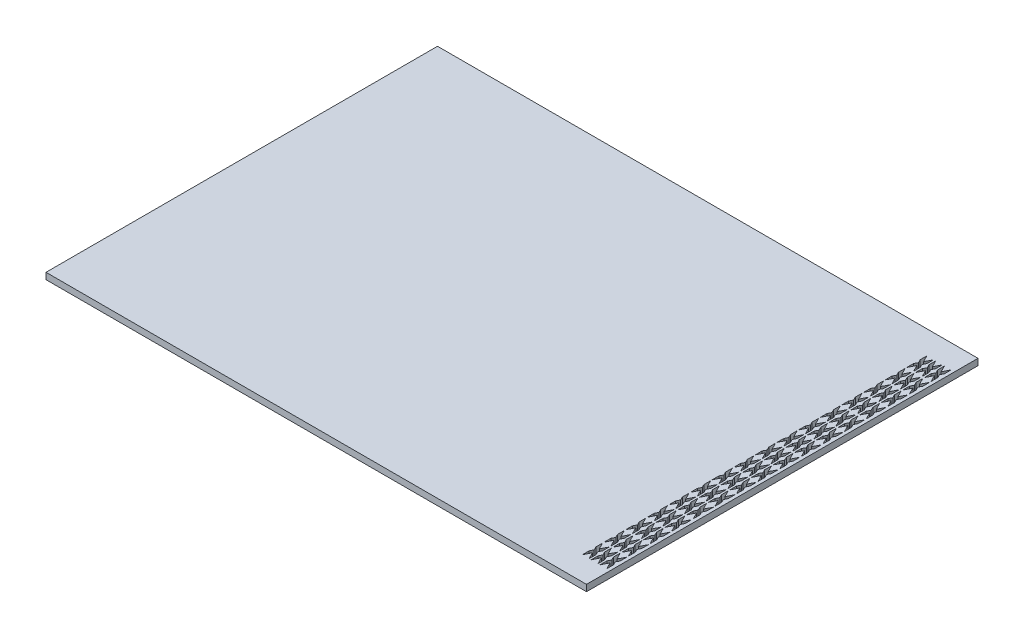
SolidWorks part; units mm, degrees
ref_plane "Front Plane" through (0, 0, 0) normal (0, 0, 1) x (1, 0, 0)
ref_plane "Top Plane" through (0, 0, 0) normal (0, 1, 0) x (1, 0, 0)
ref_plane "Right Plane" through (0, 0, 0) normal (1, 0, 0) x (0, 0, -1)
sketch "Sketch1" plane through (0, 0, 0) normal (0, 1, 0) x (1, 0, 0)
  line L1 (-66.3921, 26.7316) -> (136.8079, 26.7316)
  line L2 (-66.3921, 26.7316) -> (-66.3921, -120.4614)
  line L3 (-66.3921, -120.4614) -> (136.8079, -120.4614)
  line L4 (136.8079, 26.7316) -> (136.8079, -120.4614)
  dimension "D1" = 203.2
  dimension "D2" = 147.193
extrude "Boss-Extrude1" add sketch "Sketch1" along normal blind 2.413
sketch "Sketch2" plane through (0, 2.413, 0) normal (0, 1, 0) x (0, 0, -1)
  line L0 (-111.5714, -132.9979) -> (-109.0514, -134.2679)
  line L1 (-111.5714, -132.9979) -> (-109.0314, -132.9979)
  line L2 (-106.5314, -135.5379) -> (-103.9914, -135.5379)
  line L3 (-109.0314, -132.9979) -> (-107.7814, -133.6279)
  line L4 (-106.5314, -132.9979) -> (-107.7814, -133.6279)
  line L5 (-106.5314, -132.9979) -> (-103.9914, -132.9979)
  line L6 (-111.5714, -135.5379) -> (-109.0314, -135.5379)
  line L7 (-103.9914, -132.9979) -> (-106.5114, -134.2679)
  line L8 (-120.4614, -136.8079) -> (26.7316, -136.8079) construction
  line L9 (-120.4614, 66.3921) -> (-120.4614, -136.8079) construction
  line L10 (-107.7814, -134.908) -> (-106.5314, -135.5379)
  line L11 (-106.5114, -134.2679) -> (-103.9914, -135.5379)
  line L12 (-109.0514, -134.2679) -> (-111.5714, -135.5379)
  line L13 (-107.7814, -134.908) -> (-109.0314, -135.5379)
  dimension "D1" = 2.54
  dimension "D2" = 2.5
  dimension "D3" = 2.54
  dimension "D4" = 1.27
  dimension "D5" = 8.89
extrude "Cut-Extrude1" cut sketch "Sketch2" against normal blind 2.794
pattern_linear "LPattern1" count 16 spacing 8.128 along (0, 0, -1) count 3 spacing 3.302 along (-1, 0, 0) of "Cut-Extrude1"
